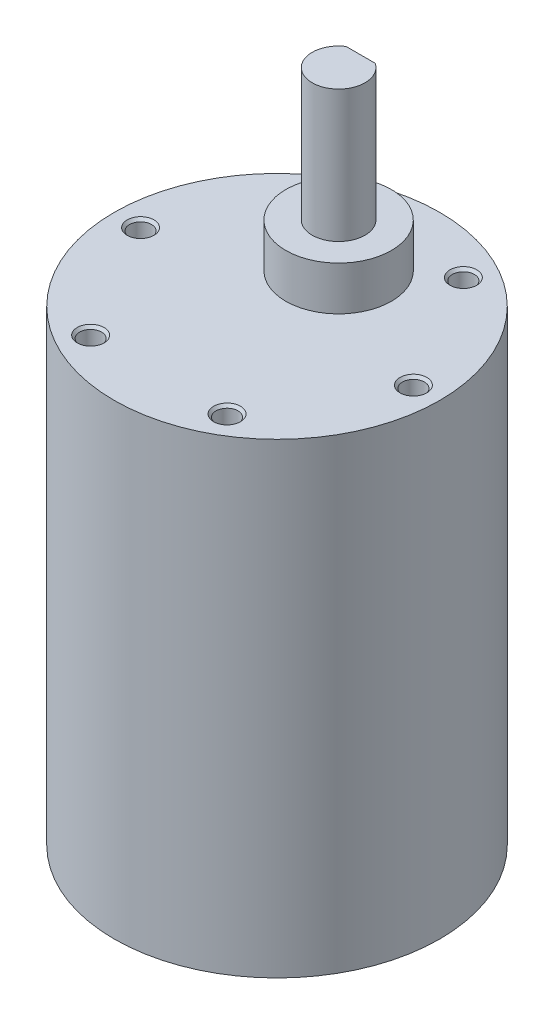
SolidWorks part; units mm, degrees
ref_plane "Front Plane" through (0, 0, 0) normal (0, 0, 1) x (1, 0, 0)
ref_plane "Top Plane" through (0, 0, 0) normal (0, 1, 0) x (1, 0, 0)
ref_plane "Right Plane" through (0, 0, 0) normal (1, 0, 0) x (0, 0, -1)
sketch "Sketch1" plane through (0, 0, 0) normal (0, 1, 0) x (1, 0, 0)
  circle A0 centre (0, 0) radius 18.5
  dimension "D1" = 37
extrude "Boss-Extrude1" add sketch "Sketch1" along normal blind 53
sketch "Sketch2" plane through (0, 53, 0) normal (0, 1, 0) x (1, 0, 0)
  line L0 (0, -0.1228) -> (0, 49999.8772) construction
  line L1 (0, 0) -> (-50000, 0) construction
  circle A0 centre (0, 7) radius 3
  circle A1 centre (0, 7) radius 6
  dimension "D2" = 6
  dimension "D4" = 12
  dimension "D3" = 7
extrude "Boss-Extrude2" add sketch "Sketch2" along normal blind 5 contours A1 A0 region at (-5.8303, 53, -7)
extrude "Boss-Extrude3" add sketch "Sketch2<3>" along normal blind 20 contours A0 region at (0, 53, -7)
sketch "Sketch2<3>" plane through (0, 53, 0) normal (0, 1, 0) x (1, 0, 0) same geometry as "Sketch2"
sketch "Sketch4" plane through (0, 73, 0) normal (0, 1, 0) x (1, 0, 0)
  line L1 (-3.7997, 12.119) -> (5.6577, 12.119)
  line L2 (-3.7997, 12.119) -> (-3.7997, 9.5)
  line L3 (-3.7997, 9.5) -> (5.6577, 9.5)
  line L4 (5.6577, 12.119) -> (5.6577, 9.5)
  circle A0 centre (0, 7) radius 3 construction
  circle A1 centre (0, 7) radius 3 construction
  point P6 (0, 4)
  dimension "D1" = 5.5
extrude "Cut-Extrude1" cut sketch "Sketch4" against normal blind 14
sketch "Sketch5" plane through (0, 53, 0) normal (0, 1, 0) x (1, 0, 0)
  line L0 (0, 0) -> (9.25, 16.0215) construction
  line L1 (0, -0.5951) -> (0, 49999.4049) construction
  circle A0 centre (0, 0) radius 18.5 construction
  circle A1 centre (0, 0) radius 15.5 construction
  point P8 (7.75, 13.4234)
  dimension "D2" = 31
  dimension "D1" = 30
hole_wizard "M3x0.5 Tapped Hole1" positions "Sketch6" profile "Sketch7" tap size "M3x0.5" standard "ANSI Metric"
sketch "Sketch6" plane through (0, 53, 0) normal (0, 1, 0) x (1, 0, 0)
  point P0 (7.75, 13.4234)
cosmetic thread "Hole Thread1" parameters "D1"=52.68, "D2"=3
sketch "Sketch7" plane through (7.75, 53, -13.4234) normal (1, 0, 0) x (0, 0, 1)
  line L0 (0, 0) -> (0, 8.7511)
  line L1 (0, 8.7511) -> (1.25, 8)
  line L2 (1.25, 8) -> (1.25, 0.3164)
  line L3 (1.25, 0.3164) -> (1.525, 0)
  line L5 (1.525, 0) -> (0, 0)
  line L6 (-1.25, 0.3164) -> (-1.525, 0) construction
  line L10 (0, 8.7511) -> (-1.25, 8) construction
  line L11 (0, -6.35) -> (0, 107.95) construction
  dimension "Tap Drill Dia." = 2.5
  dimension "Tap Drill Depth" = 8
  dimension "Near C'Sink Dia." = 3.05
  dimension "Near C'Sink Angle" = 82
  dimension "Drill Angle" = 118
pattern_circular "CirPattern1" count 6 over 360 about axis through (0, 53, 0) along (0, 1, 0) of "M3x0.5 Tapped Hole1"
cosmetic thread "Hole Thread2" parameters "D1"=52.68, "D2"=3
cosmetic thread "Hole Thread3" parameters "D1"=52.68, "D2"=3
cosmetic thread "Hole Thread4" parameters "D1"=52.68, "D2"=3
cosmetic thread "Hole Thread5" parameters "D1"=52.68, "D2"=3
cosmetic thread "Hole Thread6" parameters "D1"=52.68, "D2"=3
